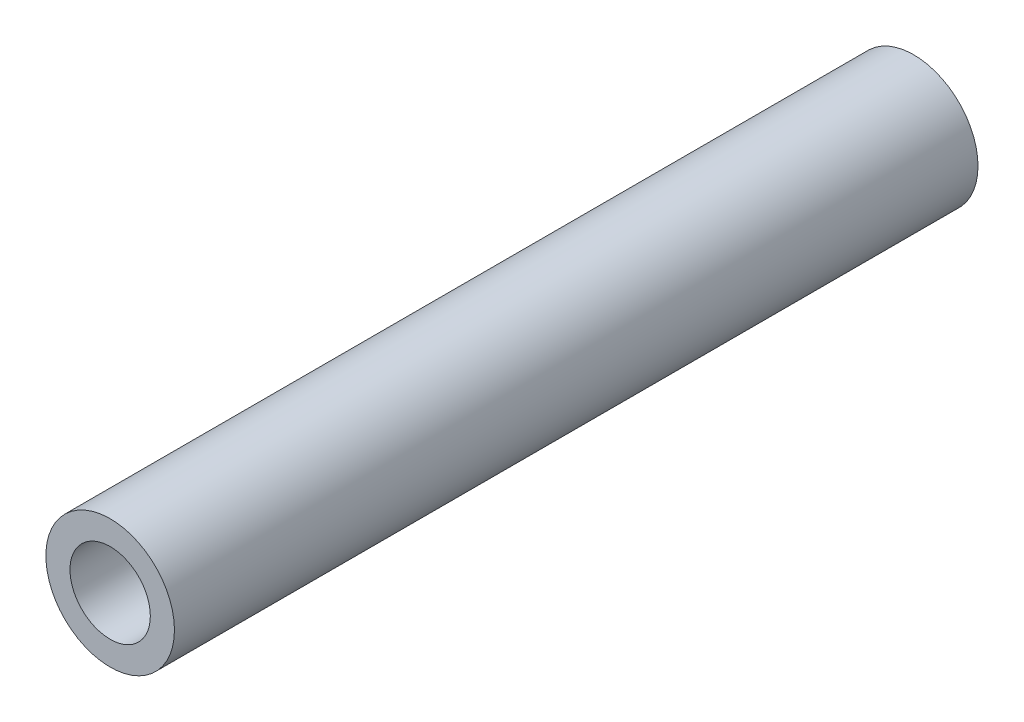
SolidWorks part; units mm, degrees
ref_plane "Front Plane" through (0, 0, 0) normal (0, 0, 1) x (1, 0, 0)
ref_plane "Top Plane" through (0, 0, 0) normal (0, 1, 0) x (1, 0, 0)
ref_plane "Right Plane" through (0, 0, 0) normal (1, 0, 0) x (0, 0, -1)
sketch "Real Length Sketch" plane through (0, 0, 0) normal (1, 0, 0) x (0, 0, -1)
  point P0 (0, 0)
  point P1 (25, 0)
  dimension "Length" = 25
sketch "Cross Section Sketch" plane through (0, 0, 0) normal (0, 0, 1) x (1, 0, 0)
  circle A0 centre (0, 0) radius 2
  circle A1 centre (0, 0) radius 1.25
  dimension "OD" = 4
  dimension "ID" = 2.5
extrude "Extrude Length" add sketch "Cross Section Sketch" along normal mid plane 25
